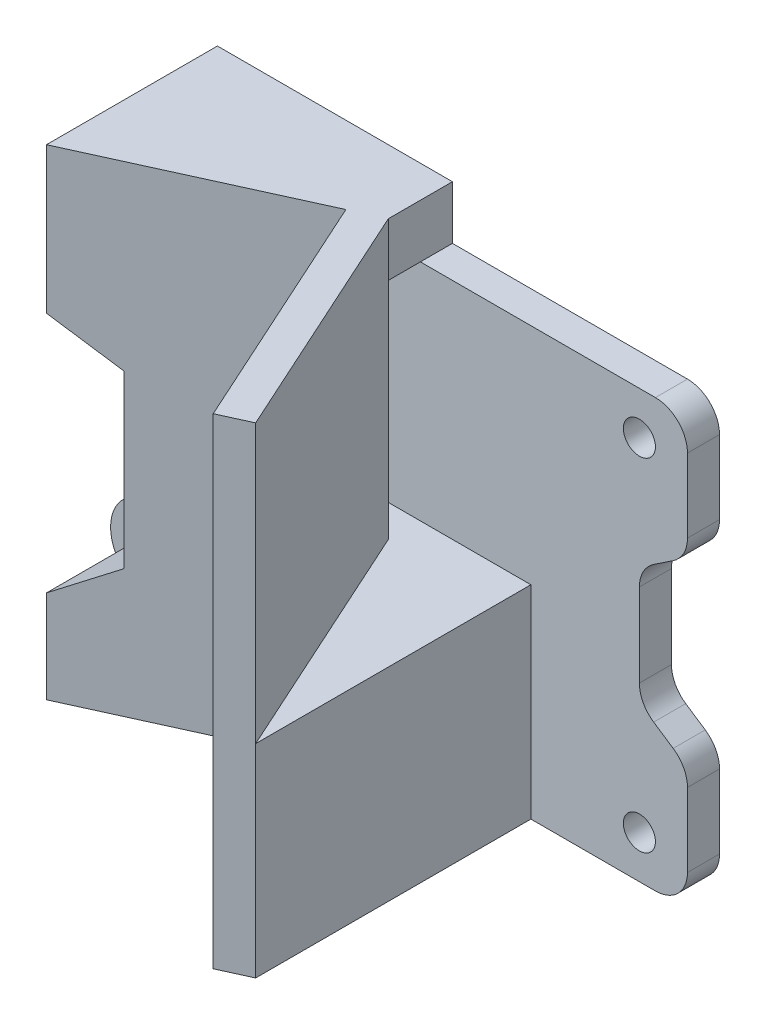
SolidWorks part; units mm, degrees
ref_plane "Alzado" through (0, 0, 0) normal (0, 0, 1) x (1, 0, 0)
ref_plane "Planta" through (0, 0, 0) normal (0, 1, 0) x (1, 0, 0)
ref_plane "Vista lateral" through (0, 0, 0) normal (1, 0, 0) x (0, 0, -1)
sketch "Croquis1" plane through (0, 0, 0) normal (0, 0, 1) x (1, 0, 0)
  line L0 (-52.1973, 0.4619) -> (-52.1973, 4.4619) construction
  line L1 (-2.1973, 16.4619) -> (-44.1973, 16.4619) construction
  line L2 (-52.1973, 4.4619) -> (-50.1973, 4.4619)
  line L3 (-52.1973, -3.5381) -> (-5.1973, -3.5381)
  line L4 (-6.6973, 0.4619) -> (-6.6973, 7.9619) construction
  line L5 (-44.1973, 24.4619) -> (-44.1973, 8.4619)
  line L6 (-44.1973, 8.4619) -> (-50.1973, 4.4619)
  line L7 (-52.1973, 32.4619) -> (-52.1973, 28.4619) construction
  line L8 (-44.1973, 24.4619) -> (-50.1973, 28.4619)
  line L9 (-52.1973, 36.4619) -> (-5.1973, 36.4619)
  line L10 (-52.1973, 28.4619) -> (-50.1973, 28.4619)
  line L11 (-2.1973, -0.5381) -> (-2.1973, 6.3563)
  line L12 (-6.6973, 7.9619) -> (-6.6973, 10.9619) construction
  line L13 (-3.5332, 8.8525) -> (-5.3614, 10.0713)
  line L14 (-6.6973, 12.5674) -> (-6.6973, 20.3563)
  line L15 (-3.5332, 24.0713) -> (-5.3614, 22.8525)
  line L16 (-2.1973, 33.4619) -> (-2.1973, 26.5674)
  arc A0 (-52.1973, 36.4619) -> (-52.1973, 28.4619) centre (-52.1973, 32.4619) ccw
  circle A1 centre (-6.6973, 32.4619) radius 1.5
  circle A2 centre (-52.1973, 0.4619) radius 1.5
  circle A3 centre (-6.6973, 0.4619) radius 1.5
  circle A4 centre (-52.1973, 32.4619) radius 1.5
  arc A5 (-5.1973, 36.4619) -> (-2.1973, 33.4619) centre (-5.1973, 33.4619) cw
  arc A6 (-52.1973, -3.5381) -> (-52.1973, 4.4619) centre (-52.1973, 0.4619) cw
  arc A7 (-5.1973, -3.5381) -> (-2.1973, -0.5381) centre (-5.1973, -0.5381) ccw
  arc A8 (-5.3614, 22.8525) -> (-6.6973, 20.3563) centre (-3.6973, 20.3563) ccw
  arc A9 (-6.6973, 12.5674) -> (-5.3614, 10.0713) centre (-3.6973, 12.5674) ccw
  arc A10 (-3.5332, 24.0713) -> (-2.1973, 26.5674) centre (-5.1973, 26.5674) ccw
  arc A11 (-2.1973, 6.3563) -> (-3.5332, 8.8525) centre (-5.1973, 6.3563) ccw
  point P22 (-2.1973, 36.4619)
  point P26 (-2.1973, -3.5381)
  point P32 (-6.6973, 16.4619)
  point P35 (-6.6973, 21.9619)
  point P41 (-2.1973, 24.9619)
  point P44 (-2.1973, 7.9619)
  dimension "D3" = 50
  dimension "D5" = 20
  dimension "D6" = 4
  dimension "D7" = 42
  dimension "D2" = 3
  dimension "D4" = 3
  dimension "D12" = 3
  dimension "D8" = 4
  dimension "D9" = 45.5
  dimension "D10" = 2
  dimension "D11" = 8
extrude "Saliente-Extruir1" add sketch "Croquis1" along normal blind 3 contours L3 A3 A2 region at (-26.7736, 16.4619, 0)
sketch "Croquis3" plane through (0, 0, 3) normal (0, 0, 1) x (1, 0, 0)
  line L3 (-49.1973, -3.5381) -> (-28.6973, -3.5381)
  line L4 (-28.6973, -3.5381) -> (-28.6973, 36.4619)
  line L5 (-52.1973, -3.5381) -> (-5.1973, -3.5381) construction
  line L6 (-52.1973, 36.4619) -> (-5.1973, 36.4619) construction
  line L7 (-28.6973, 36.4619) -> (-49.1973, 36.4619)
  line L8 (-49.1973, 36.4619) -> (-49.1973, 27.7952)
  line L9 (-44.1973, 24.4619) -> (-50.1973, 28.4619) construction
  line L10 (-49.1973, 27.7952) -> (-44.1973, 24.4619)
  line L11 (-44.1973, 24.4619) -> (-44.1973, 8.4619)
  line L12 (-44.1973, 8.4619) -> (-49.1973, 5.1286)
  line L13 (-44.1973, 8.4619) -> (-50.1973, 4.4619) construction
  line L14 (-49.1973, 5.1286) -> (-49.1973, -3.5381)
extrude "Saliente-Extruir2" add sketch "Croquis3" along normal blind 13
sketch "Croquis4" plane through (0, -3.5381, 0) normal (0, -1, 0) x (1, 0, 0)
  line L0 (-27.1973, 16) -> (-27.1973, 6.0021)
  line L1 (-27.1973, 16) -> (-27.1973, 3) construction
  line L2 (-27.1973, 16) -> (-49.1973, 16)
  line L7 (-27.1973, 6.0021) -> (-49.1973, 16)
  line L8 (-27.1973, 3) -> (-2.1973, 3) construction
  dimension "D1" = 3.0021
extrude "Cortar-Extruir1" cut sketch "Croquis4" against normal up to vertex rebuild error yes up to point (0, -27.1973, 33.4619)
sketch "Croquis6" plane through (0, 33.4619, 0) normal (0, 1, 0) x (1, 0, 0)
  line L0 (-27.1973, -6.0021) -> (-49.1973, -16)
  line L1 (-49.1973, -16) -> (-49.1973, 0)
  line L2 (-52.1973, 0) -> (-4.1973, 0) construction
  line L3 (-49.1973, 0) -> (-27.1973, 0)
  line L4 (-27.1973, 0) -> (-27.1973, -6.0021)
extrude "Saliente-Extruir4" add sketch "Croquis6" along normal blind 8
sketch "Croquis7" plane through (-27.1973, 0, 0) normal (1, 0, 0) x (0, 0, -1)
  line L0 (-6.0021, 41.4619) -> (-6.0021, 33.4619) construction
  line L1 (-6.0021, 15.4619) -> (-3, 15.4619)
  line L2 (-6.0021, 15.4619) -> (-6.0021, 36.4619)
  line L3 (-6.0021, 36.4619) -> (-3, 36.4619)
  line L4 (-3, 15.4619) -> (-3, 36.4619)
  line L5 (-6.0021, -3.5381) -> (-3, -3.5381) construction
  line L6 (-6.0021, 41.4619) -> (0, 41.4619) construction
  dimension "D1" = 19
  dimension "D2" = 5
extrude "Cortar-Extruir2" cut sketch "Croquis7" against normal up to vertex (22 mm away) up to point (-49.1973, 41.4619, 16)
sketch "Croquis8" plane through (-2.3947, 0, -5.2695) normal (0.4137, 0, 0.9104) x (0.9104, 0, -0.4137)
  line L0 (-51.4089, 41.4619) -> (-27.2436, 41.4619) construction
  line L1 (-27.2436, -3.5381) -> (-30.2436, -3.5381)
  line L2 (-27.2436, -3.5381) -> (-27.2436, 41.4619)
  line L3 (-27.2436, 41.4619) -> (-30.2436, 41.4619)
  line L4 (-30.2436, -3.5381) -> (-30.2436, 41.4619)
  dimension "D1" = 3
extrude "Saliente-Extruir5" add sketch "Croquis8" along normal blind 25
sketch "Croquis9" plane through (0, -3.5381, 0) normal (0, -1, 0) x (1, 0, 0)
  line L0 (-27.1973, 6.0021) -> (-28.6973, 6.6837)
  line L1 (-16.854, 28.762) -> (-27.1973, 6.0021)
  line L3 (-27.1973, 3) -> (-2.1973, 3) construction
  line L4 (-16.854, 3) -> (-16.854, 28.762)
  line L5 (-27.1973, 3) -> (-16.854, 3)
  line L6 (-28.6973, 6.6837) -> (-28.6973, 3)
  line L7 (-28.6973, 3) -> (-27.1973, 3)
extrude "Saliente-Extruir6" add sketch "Croquis9" against normal up to vertex (19 mm away) up to point (-28.6973, 15.4619, 3)
sketch "Croquis13" plane through (0, 0, 3) normal (0, 0, 1) x (1, 0, 0)
  line L0 (-16.854, -3.5381) -> (-5.1973, -3.5381) construction
  line L1 (-8.6973, -3.5381) -> (-7.6973, -3.5381)
  line L2 (-8.6973, -3.5381) -> (-8.6973, -1.5381)
  line L3 (-8.6973, -1.5381) -> (-7.6973, -1.5381)
  line L4 (-7.6973, -3.5381) -> (-7.6973, -1.5381)
  line L5 (-2.1973, 36.4619) -> (-2.1973, -3.5381) construction
  line L6 (-8.6973, 31.4619) -> (-7.6973, 31.4619)
  line L7 (-8.6973, 31.4619) -> (-8.6973, 33.4619)
  line L8 (-8.6973, 33.4619) -> (-7.6973, 33.4619)
  line L9 (-7.6973, 31.4619) -> (-7.6973, 33.4619)
  line L10 (-11.6973, 28.4619) -> (-12.6973, 28.4619)
  line L11 (-11.6973, -3.5381) -> (-12.6973, -3.5381)
  line L12 (-11.6973, -3.5381) -> (-11.6973, 1.4619)
  line L13 (-11.6973, 1.4619) -> (-12.6973, 1.4619)
  line L14 (-12.6973, -3.5381) -> (-12.6973, 1.4619)
  line L15 (-11.6973, 28.4619) -> (-11.6973, 33.4619)
  line L16 (-11.6973, 33.4619) -> (-12.6973, 33.4619)
  line L17 (-12.6973, 28.4619) -> (-12.6973, 33.4619)
  dimension "D1" = 5.5
  dimension "D2" = 1
  dimension "D3" = 2
  dimension "D5" = 5
  dimension "D6" = 1
  dimension "D7" = 3
  dimension "D4" = 2
  dimension "D8" = 2
sketch "Croquis14" plane through (0, 36.4619, 0) normal (0, 1, 0) x (1, 0, 0)
  line L0 (-28.6973, -16) -> (-28.6973, -9.9524)
  line L1 (-28.6973, -9.9524) -> (-29.9285, -7.2433)
  line L2 (-29.9285, -7.2433) -> (-49.1973, -16)
  line L3 (-49.1973, -16) -> (-28.6973, -16)
extrude "Cortar-Extruir3" cut sketch "Croquis14" against normal up to vertex (40 mm away) up to point (-28.6973, -3.5381, 16)
